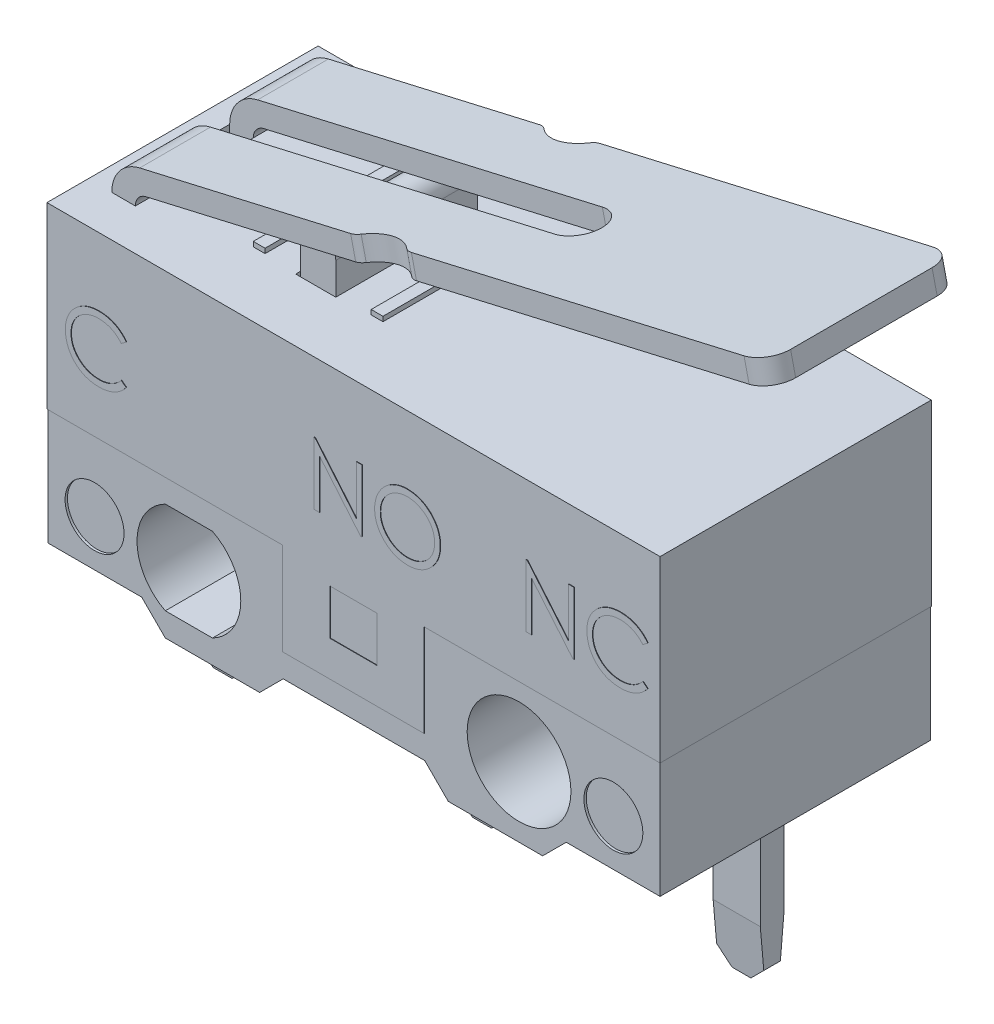
SolidWorks part; units mm, degrees
ref_plane "Plan de face" through (0, 0, 0) normal (0, 0, 1) x (1, 0, 0)
ref_plane "Plan de dessus" through (0, 0, 0) normal (0, 1, 0) x (1, 0, 0)
ref_plane "Plan de droite" through (0, 0, 0) normal (1, 0, 0) x (0, 0, -1)
sketch "Esquisse1" plane through (0, 0, 0) normal (0, 0, 1) x (1, 0, 0)
  line L1 (-6.5, 3.375) -> (6.5, 3.375)
  line L2 (-6.5, 3.375) -> (-6.5, -3.375)
  line L3 (-6.5, -3.375) -> (6.5, -3.375)
  line L4 (6.5, 3.375) -> (6.5, -3.375)
  line L5 (-6.5, 3.375) -> (6.5, -3.375) construction
  line L6 (-6.5, -3.375) -> (6.5, 3.375) construction
  point P0 (0, 0)
  dimension "D1" = 6.75
  dimension "D2" = 13
extrude "Boss.-Extru.1" add sketch "Esquisse1" along normal blind 5.75
ref_plane "Plan1" through (0, 0, 2.875) normal (0, 0, 1) x (1, 0, 0)
sketch "Esquisse6" plane through (0, 0, 5.75) normal (0, 0, 1) x (1, 0, 0)
  line L0 (-6.5, -2.875) -> (-4.5, -2.875)
  line L1 (-6.5, 3.375) -> (-6.5, -3.375) construction
  line L2 (-4.5, -2.875) -> (-4, -3.375)
  line L3 (-6.5, -3.375) -> (6.5, -3.375) construction
  line L4 (-4, -3.375) -> (-2, -3.375)
  line L5 (-2, -3.375) -> (-1.5, -2.875)
  line L6 (-1.5, -2.875) -> (1.5, -2.875)
  line L7 (1.5, -2.875) -> (2, -3.375)
  line L8 (2, -3.375) -> (4, -3.375)
  line L9 (4, -3.375) -> (4.5, -2.875)
  line L10 (4.5, -2.875) -> (6.5, -2.875)
  line L11 (6.5, -3.375) -> (6.5, 3.375) construction
  line L12 (6.5, -2.875) -> (6.5, -4.2145)
  line L13 (6.5, -4.2145) -> (-6.5, -4.2145)
  line L14 (-6.5, -4.2145) -> (-6.5, -2.875)
  dimension "D1" = 0.5
  dimension "D2" = 135
  dimension "D3" = 135
  dimension "D4" = 135
  dimension "D5" = 2
  dimension "D6" = 2
  dimension "D7" = 2
  dimension "D8" = 2
extrude "Enlèv. mat.-Extru.1" cut sketch "Esquisse6" against normal up to surface (5.75 mm away) up to face at (0, 0, 0)
sketch "Esquisse4" plane through (0, 0, 2.875) normal (0, 0, 1) x (1, 0, 0)
  line L0 (-6, -2.875) -> (-6, -6.125)
  line L9 (-5, -6.125) -> (-5, -2.875)
  line L10 (-5, -2.875) -> (-6, -2.875)
  line L11 (-5.5, -2.875) -> (-5.5, -7.9439) construction
  line L15 (-6, -6.125) -> (-5, -6.125)
  line L16 (-4.5, -2.875) -> (-6.5, -2.875) construction
  line L17 (-6.5, 3.375) -> (-6.5, -2.875) construction
  dimension "D1" = 1
  dimension "D2" = 1
  dimension "D4" = 3.25
extrude "Boss.-Extru.2" add sketch "Esquisse4" along normal blind 0.25 and the other way blind 0.25
chamfer "Chanfrein1" distance 0.3 angle 45 2 edges at (-5, -6.125, 2.875) (-6, -6.125, 2.875)
chamfer "Chanfrein2" distance 0.1 angle 85 1 edges at (-5.5, -6.125, 3.125)
pattern_linear "Répétition linéaire1" count 3 spacing 5.5 along (1, 0, 0) of "Boss.-Extru.2", "Chanfrein1", "Chanfrein2"
sketch "Esquisse7" plane through (0, 0, 5.75) normal (0, 0, 1) x (1, 0, 0)
  line L0 (-4, -2.875) -> (-3, -2.875)
  line L1 (-4, -0.9154) -> (-3, -0.9154)
  line L2 (-3.5, -1.8952) -> (3.5, -1.8952) construction
  line L3 (-4, -3.375) -> (-2, -3.375) construction
  line L4 (-6.5, 3.375) -> (-6.5, -2.875) construction
  line L5 (6.5, -2.875) -> (6.5, 3.375) construction
  arc A0 (-4, -0.9154) -> (-4, -2.875) centre (-3.5, -1.8952) ccw
  arc A1 (-3, -0.9154) -> (-3, -2.875) centre (-3.5, -1.8952) cw
  circle A2 centre (3.5, -1.8952) radius 1.1
  dimension "D1" = 1.1
  dimension "D3" = 1.1
  dimension "D4" = 2.2
  dimension "D2" = 1
  dimension "D5" = 0.5
  dimension "D6" = 3
  dimension "D7" = 3
extrude "Enlèv. mat.-Extru.2" cut sketch "Esquisse7" against normal up to surface (5.75 mm away) up to face at (0, -2, 0)
sketch "Esquisse8" plane through (0, 0, 5.75) normal (0, 0, 1) x (1, 0, 0)
  line L0 (-6.5, -0.4154) -> (-1.5, -0.4154)
  line L1 (-6.5, 3.375) -> (-6.5, -2.875) construction
  line L2 (-1.5, -0.4154) -> (-1.5, -2.375)
  line L3 (-1.5, -2.375) -> (1.5, -2.375)
  line L4 (1.5, -2.375) -> (1.5, -0.4154)
  line L5 (1.5, -0.4154) -> (6.5, -0.4154)
  line L6 (6.5, -2.875) -> (6.5, 3.375) construction
  line L7 (6.5, -0.4154) -> (6.5, -4.9919)
  line L8 (6.5, -4.9919) -> (-6.5, -4.9919)
  line L9 (-6.5, -4.9919) -> (-6.5, -0.4154)
  line L10 (1.5, -2.875) -> (-1.5, -2.875) construction
  line L11 (-3, -0.9154) -> (-4, -0.9154) construction
  line L13 (-0.5, -0.6654) -> (0.5, -0.6654)
  line L14 (-0.5, -0.6654) -> (-0.5, -1.625)
  line L15 (-0.5, -1.625) -> (0.5, -1.625)
  line L16 (0.5, -0.6654) -> (0.5, -1.625)
  line L17 (-0.5, -0.6654) -> (0.5, -1.625) construction
  line L18 (-0.5, -1.625) -> (0.5, -0.6654) construction
  point P21 (0, -1.1452)
  dimension "D1" = 0.5
  dimension "D2" = 0.5
  dimension "D3" = 0.25
  dimension "D4" = 1
  dimension "D5" = 1
  dimension "D6" = 0.75
extrude "Enlèv. mat.-Extru.3" cut sketch "Esquisse8" against normal blind 0.01
sketch "Esquisse9" plane through (0, 0, 5.74) normal (0, 0, 1) x (1, 0, 0)
  line L0 (-5.5, -1.8952) -> (5.5, -1.8952) construction
  line L1 (6.5, -2.875) -> (6.5, -0.4154) construction
  line L2 (-6.5, -0.4154) -> (-6.5, -2.875) construction
  circle A0 centre (-5.5, -1.8952) radius 0.625
  circle A1 centre (5.5, -1.8952) radius 0.625
  point P4 (3.5, -1.8952)
  dimension "D1" = 1.25
  dimension "D2" = 1.25
  dimension "D3" = 1
  dimension "D4" = 1
extrude "Enlèv. mat.-Extru.4" cut sketch "Esquisse9" against normal blind 0.05
mirror "Symétrie1" about plane through (0, 0, 2.875) normal (0, 0, 1) of "Enlèv. mat.-Extru.4", "Enlèv. mat.-Extru.3"
sketch "Esquisse10" plane through (-6.5, 0, 0) normal (-1, 0, 0) x (0, 0, 1)
  line L1 (0.01, -2.875) -> (5.74, -2.875)
  line L2 (0.01, -2.875) -> (0.01, -0.4154)
  line L3 (0.01, -0.4154) -> (5.74, -0.4154)
  line L4 (5.74, -2.875) -> (5.74, -0.4154)
extrude "Enlèv. mat.-Extru.5" cut sketch "Esquisse10" against normal blind 0.01
sketch "Esquisse11" plane through (6.5, 0, 0) normal (1, 0, 0) x (0, 0, -1)
  line L1 (-5.74, -2.875) -> (-0.01, -2.875)
  line L2 (-5.74, -2.875) -> (-5.74, -0.4154)
  line L3 (-5.74, -0.4154) -> (-0.01, -0.4154)
  line L4 (-0.01, -2.875) -> (-0.01, -0.4154)
extrude "Enlèv. mat.-Extru.6" cut sketch "Esquisse11" against normal blind 0.01
sketch "Esquisse12" plane through (0, 0, 5.75) normal (0, 0, 1) x (1, 0, 0)
  line L0 (-6.2, 0.5846) -> (-4.55, 0.5846) construction
  line L4 (-1, 0.5846) -> (2.5, 0.5846) construction
  line L5 (3.5, 0.5846) -> (6.2, 0.5846) construction
  line L6 (-1.5, -0.4154) -> (-6.5, -0.4154) construction
  line L7 (-6.5, 3.375) -> (-6.5, -0.4154) construction
  line L8 (6.5, -0.4154) -> (6.5, 3.375) construction
  text T0 "C" font "Century Gothic" height in points 5
  text T1 "NO" font "Century Gothic" height in points 5
  text T2 "NC" font "Century Gothic" height in points 5
  dimension "D1" = 1
  dimension "D2" = 1.65
  dimension "D3" = 0.3
  dimension "D4" = 0.3
  dimension "D5" = 2.7
  dimension "D6" = 3.5
  dimension "D7" = 1
extrude "Boss.-Extru.3" add sketch "Esquisse12" along normal blind 0.01
sketch "Esquisse13" plane through (0, 0, 2.875) normal (0, 0, 1) x (1, 0, 0)
  line L0 (-1.75, 4) -> (-1.75, 3.375)
  line L1 (6.5, 3.375) -> (-6.5, 3.375) construction
  line L2 (-1.75, 3.375) -> (-2.5, 3.375)
  line L3 (-2.5, 3.375) -> (-2.5, 4)
  line L4 (-4.7467, 4.375) -> (-2.1308, 4.375) construction
  line L5 (-6.5, 3.375) -> (-6.5, -0.4154) construction
  line L6 (-3.5, 3.375) -> (-3.5, 3.475)
  line L7 (-3.5, 3.475) -> (-3.25, 3.475)
  line L8 (-3.25, 3.475) -> (-3.25, 3.375)
  line L9 (-3.25, 3.375) -> (-3.5, 3.375)
  line L10 (-1, 3.375) -> (-1, 3.475)
  line L11 (-1, 3.475) -> (-0.75, 3.475)
  line L12 (-0.75, 3.475) -> (-0.75, 3.375)
  line L13 (-0.75, 3.375) -> (-1, 3.375)
  arc A0 (-2.5, 4) -> (-1.75, 4) centre (-2.125, 4) cw
  dimension "D1" = 0.75
  dimension "D2" = 1
  dimension "D3" = 4
  dimension "D4" = 0.1
  dimension "D5" = 0.75
  dimension "D6" = 0.75
  dimension "D7" = 0.25
  dimension "D8" = 0.25
extrude "Boss.-Extru.4" add sketch "Esquisse13" along normal blind 1.5 and the other way blind 1.5
sketch "Esquisse14" plane through (0, 3.375, 0) normal (0, 1, 0) x (1, 0, 0)
  line L1 (-2.5, -1.375) -> (-1.75, -1.375)
  line L2 (-2.5, -1.375) -> (-2.5, -4.375)
  line L3 (-2.5, -4.375) -> (-1.75, -4.375)
  line L4 (-1.75, -1.375) -> (-1.75, -4.375)
  line L8 (-6.5, -5.75) -> (-6.5, 0) construction
  line L9 (-6, -0.875) -> (-5.5, -0.875)
  line L10 (-6, -0.875) -> (-6, -4.875)
  line L11 (-6, -4.875) -> (-5.5, -4.875)
  line L12 (-2.55, -1.325) -> (-2.55, -4.425)
  line L13 (-2.55, -4.425) -> (-1.7, -4.425)
  line L14 (-1.7, -4.425) -> (-1.7, -1.325)
  line L15 (-1.7, -1.325) -> (-2.55, -1.325)
  line L16 (-2.55, -1.325) -> (-2.55, -4.425)
  line L17 (-2.55, -4.425) -> (-1.7, -4.425)
  line L18 (-1.7, -4.425) -> (-1.7, -1.325)
  line L19 (-1.7, -1.325) -> (-2.55, -1.325)
  line L20 (-5.5, -0.875) -> (-5.5, -4.875)
  line L21 (-6, -2.875) -> (-3.9155, -2.875) construction
  line L22 (-3.7125, -2.875) -> (3.7125, -2.875) construction
  dimension "D2" = 0.5
  dimension "D3" = 0.5
  dimension "D4" = 4
  dimension "D1" = 0.05
extrude "Enlèv. mat.-Extru.7" cut sketch "Esquisse14" against normal blind 2
sketch "Esquisse16" plane through (0, 0, 0.875) normal (0, 0, 1) x (1, 0, 0)
  line L0 (-6, 2.375) -> (-5.5, 2.375)
  line L1 (-5.5, 2.375) -> (-5.5, 3.375)
  line L2 (-5.2748, 3.6581) -> (8, 6.7211)
  line L3 (8, 6.7211) -> (7.8921, 7.1888)
  line L4 (7.8921, 7.1888) -> (-5.4072, 4.1201)
  line L5 (-6, 3.375) -> (-6, 2.375)
  line L6 (-6.5, 3.375) -> (-6.5, -0.4154) construction
  line L7 (6.5, 3.375) -> (-6.5, 3.375) construction
  line L8 (8, 6.7211) -> (8, 3.9001) construction
  line L9 (6.5, -0.4154) -> (6.5, 3.375) construction
  line L10 (6.5, 2.5145) -> (6.5, 9.8405) construction
  arc A0 (-5.5, 3.375) -> (-5.2748, 3.6581) centre (-5.2095, 3.375) cw
  arc A2 (-1.75, 4) -> (-2.5, 4) centre (-2.125, 4) ccw construction
  arc A3 (-6, 3.375) -> (-5.4072, 4.1201) centre (-5.2353, 3.375) cw
  point P8 (6.5, 6.375)
  dimension "D1" = 0.5
  dimension "D2" = 0.5
  dimension "D3" = 0.48
  dimension "D4" = 1
  dimension "D5" = 1.5
  dimension "D6" = 3
extrude "Boss.-Extru.13" add sketch "Esquisse16" along normal up to surface (4 mm away) separate body contours A3 L4 L3 L2 A0 L1 L0 L5 up to face at (-5.75, 2.375, 4.875)
sketch "Esquisse17" plane through (0, 0, 2.875) normal (0, 0, 1) x (1, 0, 0)
  line L6 (-5.4072, 4.1201) -> (2.3879, 5.9188)
  line L7 (7.8921, 7.1888) -> (-5.4072, 4.1201) construction
  line L8 (2.3879, 5.9188) -> (2.4959, 5.4511)
  line L9 (-5.2748, 3.6581) -> (8, 6.7211) construction
  line L10 (2.4959, 5.4511) -> (-5.2748, 3.6581)
  line L12 (-6, 3.375) -> (-6, 2.375)
  line L13 (-6, 2.375) -> (-5.5, 2.375)
  line L14 (-5.5, 2.375) -> (-5.5, 3.375)
  line L15 (-5.2748, 3.6581) -> (8, 6.7211)
  line L16 (8, 6.7211) -> (7.8921, 7.1888)
  line L17 (7.8921, 7.1888) -> (-5.4072, 4.1201)
  line L18 (-6, 3.375) -> (-6, 2.375)
  line L19 (-6, 2.375) -> (-5.5, 2.375)
  line L20 (-5.5, 2.375) -> (-5.5, 3.375)
  arc A4 (-5.4072, 4.1201) -> (-6, 3.375) centre (-5.2353, 3.375) ccw
  arc A5 (-5.2748, 3.6581) -> (-5.5, 3.375) centre (-5.2095, 3.375) ccw
  arc A6 (-5.4072, 4.1201) -> (-6, 3.375) centre (-5.2353, 3.375) ccw
  arc A7 (-5.2748, 3.6581) -> (-5.5, 3.375) centre (-5.2095, 3.375) ccw
  dimension "D2" = 8
  dimension "D1" = 0
extrude "Enlèv. mat.-Extru.8" cut sketch "Esquisse17" against normal blind 0.5 and the other way blind 0.5
fillet "Congé1" radius 0.5 2 edges at (2.4419, 5.6849, 3.375) (2.4419, 5.6849, 2.375)
sketch "Esquisse18" plane through (-1.176, 5.0964, 0) normal (-0.2248, 0.9744, 0) x (0.9744, 0.2248, 0)
  line L0 (3.6575, -1.5522) -> (3.6575, -4.3731) construction
  line L1 (1.6575, 0.7356) -> (1.6575, -6.4529) construction
  line L3 (1.6575, -4.625) -> (-0.9803, -4.625) construction
  line L4 (9.3063, -4.875) -> (-4.3425, -4.875) construction
  line L5 (1.6575, -1.125) -> (-0.2394, -1.125) construction
  line L6 (9.3063, -0.875) -> (-4.3425, -0.875) construction
  arc A0 (3.6575, -2.875) -> (3.1575, -2.375) centre (3.1575, -2.875) ccw construction
  circle A1 centre (0.9075, -5.375) radius 0.75
  circle A2 centre (0.9075, -0.375) radius 0.75
  dimension "D2" = 1.5
  dimension "D3" = 1.5
  dimension "D1" = 2
  dimension "D4" = 0.25
  dimension "D5" = 0.25
extrude "Enlèv. mat.-Extru.9" cut sketch "Esquisse18" against normal blind 0.5
fillet "Congé2" radius 0.25 4 edges at (-0.7824, 4.941, 0.875) (0.307, 5.1923, 0.875) (0.307, 5.1923, 4.875) (-0.7824, 4.941, 4.875)
fillet "Congé3" radius 0.5 2 edges at (7.946, 6.955, 0.875) (7.946, 6.955, 4.875)
sketch "Esquisse19" plane through (0, 0, 0) normal (0, 0, -1) x (-1, 0, 0)
  line L0 (-4.5, -0.1654) -> (5.7239, -0.1654) construction
  line L1 (-6.5, -0.4154) -> (-1.5, -0.4154) construction
  line L2 (-6.5, -0.4154) -> (-6.5, 3.375) construction
  text T0 "2A125VAC" font "Century Gothic" height in points 4
  dimension "D1" = 0.25
  dimension "D2" = 2
extrude "Boss.-Extru.14" add sketch "Esquisse19" along normal blind 0.05
